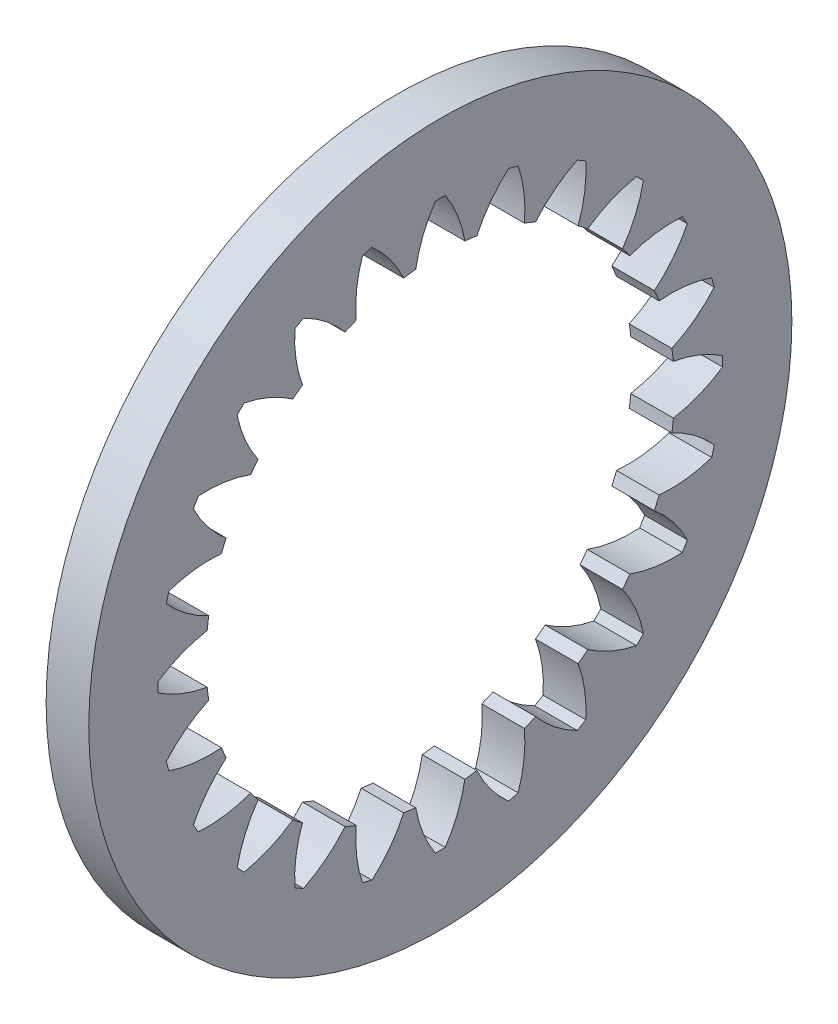
SolidWorks part; units mm, degrees
ref_plane "Plane1" through (0, 0, 0) normal (0, 0, 1) x (1, 0, 0)
ref_plane "Plane2" through (0, 0, 0) normal (0, 1, 0) x (1, 0, 0)
ref_plane "Plane3" through (0, 0, 0) normal (1, 0, 0) x (0, 0, -1)
sketch "HoldingSke" plane through (0, 0, 0) normal (0, 1, 0) x (1, 0, 0)
  line L0 (0, 0) -> (0.9135, -0.4067)
  line L1 (-15, 0) -> (100, 0) construction
  line L2 (0, 0) -> (-2.1039, 2.3779)
  line L3 (0, 0) -> (-11.863, 4.5341)
  line L4 (0, 0) -> (7.8894, 3.5126)
  line L5 (0, 0) -> (-23.7986, -8.8762)
  line L6 (0, 0) -> (-10.5278, -7.1032)
  line L7 (-2.1039, 2.3779) -> (3.3635, 27.1825)
  line L8 (-76.2, 3.3779) -> (-54.61, 3.3779)
  line L9 (-67.7845, 28.3722) -> (-49.3413, 33.142)
  line L10 (-76.2, 71.12) -> (104.1128, 71.12)
  line L11 (0, 0) -> (-2, 0)
  line L12 (-76.2, 101.6) -> (-76.162, 101.6)
  line L13 (24.9733, 27.94) -> (52.9518, 28.4284)
  line L14 (24.9733, 27.94) -> (24.9743, 27.94)
  line L15 (24.9733, 27.94) -> (100.4006, 29.5858)
  circle A0 centre (0, 0) radius 16.5
  circle A1 centre (0, 0) radius 12.7
  circle A2 centre (0, 0) radius 12.7
  dimension "Num_teeth" = 24
  dimension "Pitch_radius" = 180.3128
  dimension "Width" = 2
  dimension "Diameter" = 33
sketch "BasProSke" plane through (0, 0, 0) normal (0, 1, 0) x (1, 0, 0)
  line L0 (-10, 0) -> (60, 0) construction
  line L1 (0, 11) -> (0, 16.5)
  line L2 (0, 11) -> (2, 11)
  line L3 (2, 11) -> (2, 16.5)
  line L4 (2, 16.5) -> (0, 16.5)
  dimension "Thickness" = 2
  dimension "Diameter" = 33
revolve "Base-Revolve" add sketch "BasProSke" angle 360 about L0
sketch "TooCutSke" plane through (0, 0, 0) normal (1, 0, 0) x (0, 0, -1)
  line L3 (0.8798, 11.9677) -> (0.8798, 53.6633) construction
  line L4 (0, 0) -> (0, 59.563) construction
  line L5 (0, 0) -> (-8.9185, 67.7429) construction
  line L6 (-4.7598, 9.9196) -> (36.1543, 15.306) construction
  circle A0 centre (0, 0) radius 12 construction
  circle A1 centre (0, 0) radius 13.251 construction
  circle A2 centre (0, 0) radius 10.456 construction
  circle A3 centre (0, 0) radius 10.9746 construction
  arc A4 (1.1573, 10.9134) -> (0.2317, 13.249) centre (-4.7598, 9.9196) ccw
  arc A5 (1.1573, 10.9134) -> (-1.1573, 10.9134) centre (0, 0) ccw
  arc A6 (0.2317, 13.249) -> (-0.2317, 13.249) centre (0, 0) ccw
  arc A7 (-0.2317, 13.249) -> (-1.1573, 10.9134) centre (4.7598, 9.9196) ccw
extrude "ToothCut" cut sketch "TooCutSke" along normal through all
fillet "Breaks" [suppressed] radius 0.1
fillet "RootFillets" [suppressed] radius 0.251
pattern_circular "TeethCuts" count 24 every 15 about axis through (-10, 0, 0) along (1, 0, 0) of "RootFillets", "Breaks", "ToothCut"
equation "' \"Module@HoldingSke\" = 6.35"
equation "' \"Num_teeth@HoldingSke\" = 24"
equation "' \"Ap@HoldingSke\" =  14.5"
equation "' \"Ap@HoldingSke\" = 14.5"
equation "' \"Width@HoldingSke\" = 12"
equation "' \"Diameter@HoldingSke\" = 8 * 25.4"
equation "' \"Show_teeth@HoldingSke\" = 100"
equation "' \"Backlash@HoldingSke\" = 0.009 * 25.4"
equation "' \"Addendum_fac@HoldingSke\" = 1.0"
equation "' \"Dedendum_fac@HoldingSke\" = 1.25"
equation "' \"Dedendum_add@HoldingSke\" = 0.00005 * 25.4"
equation "' \"Clearance_fac@HoldingSke\" = 0.25"
equation "\"Pitch@HoldingSke\" = 1 / \"Module@HoldingSke\" "
equation "\"Overcut_dia@TooCutSke\" = (\"Num_teeth@HoldingSke\" - 2 * \"Addendum_fac@HoldingSke\") / \"Pitch@HoldingSke\" - 0.002 * 25.4"
equation "\"Pitch_dia@TooCutSke\" = \"Num_teeth@HoldingSke\" / \"Pitch@HoldingSke\""
equation "\"Base_dia@TooCutSke\" = \"Num_teeth@HoldingSke\" / \"Pitch@HoldingSke\" * cos((\"Ap@HoldingSke\"  * 3.14159265 / 180)) * 0.90"
equation "\"Root_dia@TooCutSke\" = \"Num_teeth@HoldingSke\"  / \"Pitch@HoldingSke\" + 2 *  \"Dedendum_fac@HoldingSke\"/ \"Pitch@HoldingSke\" + \"Dedendum_add@HoldingSke\" * 2"
equation "\"Half_ang@TooCutSke\" = 180 / \"Num_teeth@HoldingSke\""
equation "\"Half_CT@TooCutSke\" = \"Num_teeth@HoldingSke\" / \"Pitch@HoldingSke\" * sin((3.14159265 / 2 / \"Num_teeth@HoldingSke\")) / 2 + 10 * \"Backlash@HoldingSke\" / 4"
equation "\"Flank_rad@TooCutSke\" = \"Num_teeth@HoldingSke\" / \"Pitch@HoldingSke\" / 4"
equation "\"Radius@RootFillets\"= \"Clearance_fac@HoldingSke\" / \"Pitch@HoldingSke\" + \"Dedendum_add@HoldingSke\""
equation "\"Break_rad@Breaks\" = 0.02 / \"Pitch@HoldingSke\" * 5"
equation "\"Num_teeth@TeethCuts\" = int( \"Show_teeth@HoldingSke\" ) + 1"
equation "\"Num_teeth@TeethCuts\" = ((sgn( \"Num_teeth@TeethCuts\" - \"Num_teeth@HoldingSke\" )-1)*( \"Num_teeth@TeethCuts\" - \"Num_teeth@HoldingSke\" ))/-2+ \"Num_teeth@HoldingSke\""
equation "\"Num_teeth@TeethCuts\" = ((sgn( \"Num_teeth@TeethCuts\" - 2.0)+1)*( \"Num_teeth@TeethCuts\" - 2.0))/2 +2.0"
equation "\"Angle@TeethCuts\" = 360.0 / \"Num_teeth@HoldingSke\""
equation "\"Diameter@BasProSke\" = \"Num_teeth@HoldingSke\"  / \"Pitch@HoldingSke\" + 2 *  \"Dedendum_fac@HoldingSke\"/ \"Pitch@HoldingSke\" + \"Dedendum_add@HoldingSke\" * 2 + 0.002 * 25.4"
equation "\"Diameter@BasProSke\" = ((sgn( \"Diameter@BasProSke\"  - \"Diameter@HoldingSke\" )+1)*( \"Diameter@BasProSke\"  - \"Diameter@HoldingSke\" ))/2 + \"Diameter@HoldingSke\""
equation "\"Inside_diameter@BasProSke\" =  (\"Num_teeth@HoldingSke\" - 2 * \"Addendum_fac@HoldingSke\") / \"Pitch@HoldingSke\" "
equation "\"Thickness@BasProSke\"  = \"Width@HoldingSke\""
